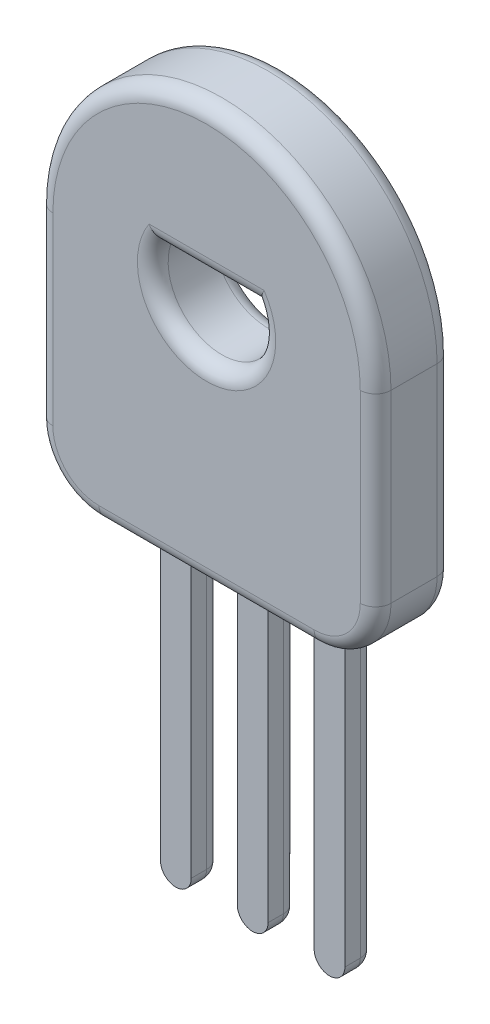
SolidWorks part; units mm, degrees
ref_plane "Front Plane" through (0, 0, 0) normal (0, 0, 1) x (1, 0, 0)
ref_plane "Top Plane" through (0, 0, 0) normal (0, 1, 0) x (1, 0, 0)
ref_plane "Right Plane" through (0, 0, 0) normal (1, 0, 0) x (0, 0, -1)
sketch "Sketch1" plane through (0, 0, 0) normal (0, 0, 1) x (1, 0, 0)
  line L0 (-5.5, 0) -> (-5.5, -8)
  line L1 (5.5, 0) -> (5.5, -8)
  line L2 (5.5, -8) -> (-5.5, -8)
  line L3 (-1.5811, 0.75) -> (1.5811, 0.75)
  line L4 (0, -1.75) -> (3.0538, -1.75) construction
  line L5 (0, 0) -> (0, -14.342) construction
  line L9 (-2.5, -8) -> (-2.5, -18) construction
  line L10 (-2, -8) -> (-2, -18)
  line L11 (-3, -8) -> (-3, -18)
  line L12 (0, -8) -> (0, -18) construction
  line L13 (0.5, -8) -> (0.5, -18)
  line L14 (-0.5, -8) -> (-0.5, -18)
  line L15 (2.5, -8) -> (2.5, -18) construction
  line L16 (3, -8) -> (3, -18)
  line L17 (2, -8) -> (2, -18)
  arc A0 (-1.5811, 0.75) -> (1.5811, 0.75) centre (0, 0) ccw
  arc A1 (5.5, 0) -> (-5.5, 0) centre (0, 0) ccw
  arc A3 (-3, -18) -> (-2, -18) centre (-2.5, -18) ccw
  arc A5 (-0.5, -18) -> (0.5, -18) centre (0, -18) ccw
  arc A7 (2, -18) -> (3, -18) centre (2.5, -18) ccw
  point P17 (-2.5, -10.5)
  point P22 (0, -10.5)
  point P27 (2.5, -10.5)
  dimension "D1" = 3.5
  dimension "D2" = 11
  dimension "D3" = 8
  dimension "D4" = 2.5
  dimension "D5" = 10
  dimension "D8" = 1
  dimension "D9" = 1
  dimension "D10" = 1
extrude "Boss-Extrude1" add sketch "Sketch1" along normal blind 2.5 contours L1 A1 L0 L2 A0 L3 region at (0, -1.8605, 0)
extrude "Boss-Extrude2" add sketch "Sketch1<3>" along normal blind 1 contours L11 A3 L10 L2 | L14 A5 L13 L2 | L17 A7 L16 L2 region at (-2.5, -13.1969, 0) region at (2.5, -13.1969, 0) region at (0, -13.1969, 0)
sketch "Sketch1<3>" plane through (0, 0, 0) normal (0, 0, 1) x (1, 0, 0) same geometry as "Sketch1"
fillet "Fillet1" radius 2 2 edges at (5.5, -8, 1.25) (-5.5, -8, 1.25)
fillet "Fillet2" radius 0.5 28 edges at (0, 5.5, 0) (-5.5, -3, 0) (-4.9142, -7.4142, 0) (-3.25, -8, 0) (-3, -13, 0) (-2.5, -18.5, 0) (-2, -13, 0) (-1.25, -8, 0) (-0.5, -13, 0) (0, -18.5, 0) (0.5, -13, 0) (1.25, -8, 0) (2, -13, 0) (2.5, -18.5, 0) (3, -13, 0) (3.25, -8, 0) (4.9142, -7.4142, 0) (5.5, -3, 0) (0, 0.75, 0) (0, -1.75, 0) (-4.9142, -7.4142, 2.5) (-5.5, -3, 2.5) (0, 5.5, 2.5) (5.5, -3, 2.5) (4.9142, -7.4142, 2.5) (0, -8, 2.5) (0, 0.75, 2.5) (0, -1.75, 2.5)
